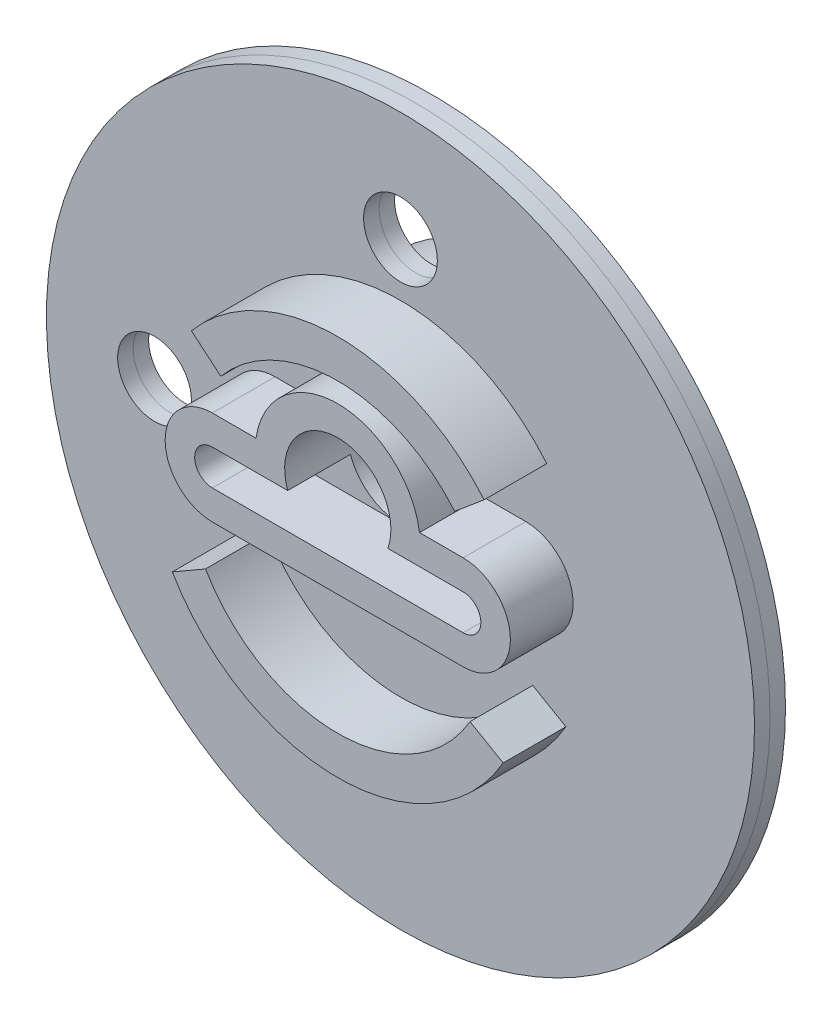
SolidWorks part; units mm, degrees
ref_plane "Front Plane" through (0, 0, 0) normal (0, 0, 1) x (1, 0, 0)
ref_plane "Top Plane" through (0, 0, 0) normal (0, 1, 0) x (1, 0, 0)
ref_plane "Right Plane" through (0, 0, 0) normal (1, 0, 0) x (0, 0, -1)
sketch "Sketch1" plane through (0, 0, 0) normal (0, 0, 1) x (1, 0, 0)
  line L0 (0, 29.8051) -> (0, -31.034) construction
  line L1 (0, 24) -> (30.3616, 24) construction
  line L2 (0, 10.425) -> (27.4702, 10.425) construction
  line L7 (0, 7.983) -> (0, -1.8885) construction
  circle A0 centre (0, 0) radius 24
  point P10 (-7.5124, 8.4374)
  point P12 (9.4132, 9.0185)
  point P13 (7.5124, 8.4374)
  point P25 (-3.5248, 8.4374)
  point P28 (-7.5124, 8.4374)
  point P29 (11.5, 8.4374)
  point P31 (-5.6117, 9.0185)
  point P32 (7.5124, 8.4374)
  dimension "D3" = 48
extrude "Boss-Extrude2" add sketch "Sketch1" along normal blind 2.1
sketch "Sketch3" plane through (0, 0, 2.1) normal (0, 0, 1) x (1, 0, 0)
  line L0 (0, 23.901) -> (0, 17.4278) construction
  line L2 (0, 7.01) -> (23.6909, 7.01) construction
  line L3 (-39.9699, 21.16) -> (18.4653, 21.16) construction
  circle A0 centre (0, 0) radius 21.16 construction
  circle A1 centre (0, 3.41) radius 3.6
  circle A2 centre (0, 0) radius 24 construction
  dimension "D1" = 7.2
  dimension "D2" = 42.32
  dimension "D3" = 14.15
extrude "Cut-Extrude1" cut sketch "Sketch3" against normal through all and the other way through all
sketch "Sketch6" plane through (0, 0, 0) normal (0, 0, -1) x (-1, 0, 0)
  circle A2 centre (0, 3.595) radius 4.85
  circle A6 centre (0, 3.41) radius 3.6
  circle A7 centre (0, 3.41) radius 3.6
  dimension "D2" = 0
  dimension "D1" = 9.7
extrude "Boss-Extrude5" add sketch "Sketch6" along normal blind 2.2
sketch "Sketch7" plane through (0, 0, 0) normal (0, 0, -1) x (-1, 0, 0)
  circle A0 centre (0, 0) radius 10
  circle A1 centre (0, 0) radius 11.25
  dimension "D1" = 20
  dimension "D2" = 22.5
extrude "Boss-Extrude6" add sketch "Sketch7" along normal blind 6
sketch "Sketch8" plane through (0, 0, 0) normal (1, 0, 0) x (0, 0, -1)
  line L0 (-1.05, 24) -> (-1.05, -24)
  line L1 (0, 24) -> (-2.1, 24) construction
  line L2 (-2.1, -24) -> (0, -24) construction
split "Split1" trim tools "Sketch8" bodies to split 109 resulting bodies 110 111
sketch "Sketch9" plane through (0, 0, 2.1) normal (0, 0, 1) x (1, 0, 0)
  line L0 (0, 24.1336) -> (0, -27.3818) construction
  line L1 (-9.7, -0.443) -> (-9.7, 3.9046) construction
  line L2 (9.7, -0.443) -> (9.7, 5.0091) construction
  line L3 (-8.5, -0.19) -> (8.5, -0.19)
  line L4 (0, -0.19) -> (14.2995, -0.19) construction
  line L5 (-8.5, -2.19) -> (8.5, -2.19)
  line L6 (-8.5, 4.21) -> (-5.5426, 4.21)
  line L7 (-8.5, 2.21) -> (-3.3941, 2.21)
  line L8 (5.5426, 4.21) -> (8.5, 4.21)
  line L9 (3.3941, 2.21) -> (8.5, 2.21)
  arc A0 (-8.5, 2.21) -> (-8.5, -0.19) centre (-8.5, 1.01) ccw
  arc A1 (8.5, -0.19) -> (8.5, 2.21) centre (8.5, 1.01) ccw
  circle A2 centre (0, 3.41) radius 3.6 construction
  arc A3 (-8.5, 4.21) -> (-8.5, -2.19) centre (-8.5, 1.01) ccw
  arc A5 (8.5, -2.19) -> (8.5, 4.21) centre (8.5, 1.01) ccw
  circle A6 centre (-8.5, 1.01) radius 1.2 construction
  arc A8 (5.5426, 4.21) -> (-5.5426, 4.21) centre (0, 3.41) ccw
  circle A9 centre (-8.5, 1.01) radius 3.2 construction
  circle A10 centre (8.5, 1.01) radius 3.2 construction
  circle A11 centre (8.5, 1.01) radius 1.2 construction
  circle A13 centre (0, 3.41) radius 3.6
  arc A14 (3.3941, 2.21) -> (-3.3941, 2.21) centre (0, 3.41) ccw
  point P3 (-7.3524, 1.3608)
  point P18 (11.7, 1.01)
  point P20 (9.6476, 1.3608)
  point P31 (-5.3, 1.01)
  dimension "D1" = 2.4
  dimension "D2" = 19.4
  dimension "D3" = 2
  dimension "D4" = 0
  dimension "D5" = 2
extrude "Boss-Extrude7" add sketch "Sketch9" along normal blind 4.25
sketch "Sketch5" plane through (0, 0, 2.1) normal (0, 0, 1) x (1, 0, 0)
  line L2 (0, 0) -> (0, 14.2168) construction
  line L5 (7.9286, 6.6529) -> (9.9203, 8.3241)
  line L6 (-7.9286, 6.6529) -> (-9.9203, 8.3241)
  line L7 (-8.9634, -5.175) -> (-11.215, -6.475)
  line L8 (8.9634, -5.175) -> (11.215, -6.475)
  arc A2 (-8.9634, -5.175) -> (8.9634, -5.175) centre (0, 0) ccw
  arc A3 (7.9286, 6.6529) -> (-7.9286, 6.6529) centre (0, 0) ccw
  circle A4 centre (0, 0) radius 10.35 construction
  arc A5 (-11.215, -6.475) -> (11.215, -6.475) centre (0, 0) ccw
  circle A6 centre (0, 0) radius 12.95 construction
  arc A7 (9.9203, 8.3241) -> (-9.9203, 8.3241) centre (0, 0) ccw
  point P3 (0, 0)
  point P4 (9.8978, 3.026)
  point P5 (12.95, 0)
  point P6 (12.95, 0)
  point P13 (9.8978, 3.026)
  dimension "D1" = 100
  dimension "D5" = 20.7
  dimension "D3" = 120
  dimension "D4" = 60
  dimension "D2" = 50
  dimension "D6" = 2.6
extrude "Boss-Extrude4" add sketch "Sketch5" along normal blind 4.25
sketch "Sketch10" plane through (0, 0, 2.1) normal (0, 0, 1) x (1, 0, 0)
  line L0 (0, 0) -> (-28.718, 0) construction
  line L1 (0, 0) -> (0, 22.4733) construction
  circle A0 centre (0, 16.5276) radius 2.5
  circle A1 centre (-16.6705, 0) radius 2.5
  dimension "D1" = 5
  dimension "D2" = 5
extrude "Cut-Extrude2" cut sketch "Sketch10" against normal through all
